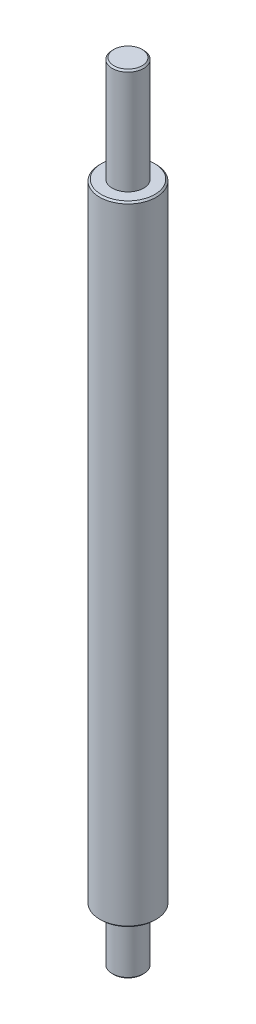
SolidWorks part; units mm, degrees
material "Q235-A"
ref_plane "前视基准面" through (0, 0, 0) normal (0, 0, 1) x (1, 0, 0)
ref_plane "上视基准面" through (0, 0, 0) normal (0, 1, 0) x (1, 0, 0)
ref_plane "右视基准面" through (0, 0, 0) normal (1, 0, 0) x (0, 0, -1)
sketch "草图1" plane through (0, 0, 0) normal (0, 0, 1) x (1, 0, 0)
  line L0 (0, 0) -> (0, -254.9533) construction
  line L2 (0, 0) -> (0, -250.5)
  line L3 (0, -250.5) -> (-5, -250.5)
  line L4 (-5, -250.5) -> (-5, -233.5)
  line L5 (-5, -233.5) -> (-9, -233.5)
  line L7 (-9, -33.5) -> (-5, -33.5)
  line L12 (-9, -233.5) -> (-9, -33.5)
  line L19 (-5, -33.5) -> (-5, 0)
  line L20 (-5, 0) -> (0, 0)
  dimension "D1" = 10
  dimension "D2" = 200
  dimension "D3" = 33.5
  dimension "D4" = 10
  dimension "D5" = 18
  dimension "D7" = 17
revolve "旋转1" add sketch "草图1" angle 360 about L2
chamfer "倒角1" distance 0.5 angle 45 4 edges at (-5, -250.5, 0) (-5, 0, 0) (-9, -233.5, 0) (-9, -33.5, 0)
chamfer "倒角2" [suppressed] distance 0.2 angle 45
ref_plane "基准面1" through (0, 0, -9) normal (0, 0, 1) x (1, 0, 0)
sketch "草图4" plane through (0, 0, -9) normal (0, 0, 1) x (1, 0, 0)
  line L0 (0, 80.5) -> (0, -80.5)
  point P3 (0, 32.5)
  point P4 (0, -32.5)
  dimension "D1" = 48
  dimension "D2" = 48
  dimension "D3" = 32.5
hole_wizard "Ø6.0 (6) 直径孔1" positions "草图6" profile "草图5" hole size "Ø6.0" standard "GB"
sketch "草图6" plane through (0, 0, -9) normal (0, 0, 1) x (1, 0, 0)
  line L1 (0, 0) -> (0, -269.1262) construction
  line L3 (9, -133.5) -> (-66.6543, -133.5) construction
  line L4 (9, -233) -> (9, -34) construction
  point P0 (0, -214)
  point P3 (0, -166)
  point P6 (0, -101)
  point P9 (0, -53)
  dimension "D1" = 32.5
  dimension "D2" = 48
  dimension "D3" = 32.5
  dimension "D4" = 48
sketch "草图5" plane through (0, -214, -9) normal (1, 0, 0) x (0, 1, 0)
  line L0 (0, 0) -> (0, 3.8026)
  line L1 (0, 3.8026) -> (3, 2)
  line L2 (3, 2) -> (3, 0)
  line L5 (3, 0) -> (0, 0)
  line L10 (0, 3.8026) -> (-3, 2) construction
  line L11 (0, -6.35) -> (0, 107.95) construction
  dimension "孔直径" = 6
  dimension "孔深度" = 2
  dimension "导头角度" = 118
pattern_circular "阵列(圆周)1" count 2 over 90 about axis through (0, 0, 0) along (0, 1, 0) of "Ø6.0 (6) 直径孔1"
sketch "草图3" plane through (0, 0, 0) normal (0, 1, 0) x (1, 0, 0)
  line L1 (-6.6073, 9.3914) -> (9.8332, 9.3914)
  line L2 (-6.6073, 9.3914) -> (-6.6073, 4)
  line L3 (-6.6073, 4) -> (9.8332, 4)
  line L4 (9.8332, 9.3914) -> (9.8332, 4)
  dimension "D1" = 4
extrude "切除-拉伸2" [suppressed] cut sketch "草图3" against normal blind 15
